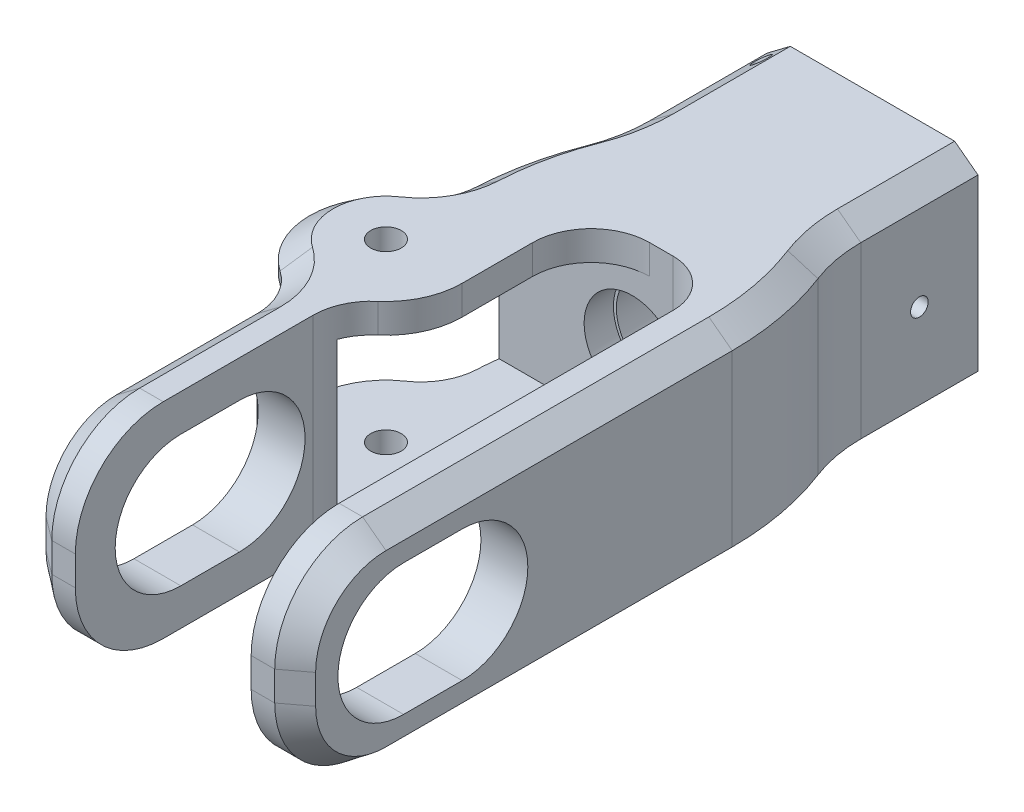
SolidWorks part; units mm, degrees
ref_plane "Front Plane" through (0, 0, 0) normal (0, 0, 1) x (1, 0, 0)
ref_plane "Top Plane" through (0, 0, 0) normal (0, 1, 0) x (1, 0, 0)
ref_plane "Right Plane" through (0, 0, 0) normal (1, 0, 0) x (0, 0, -1)
sketch "Sketch1" plane through (0, 0, 0) normal (0, 0, 1) x (1, 0, 0)
  line L1 (23, 17.5) -> (-23, 17.5)
  line L2 (23, 17.5) -> (23, -17.5)
  line L3 (23, -17.5) -> (-23, -17.5)
  line L4 (-23, 17.5) -> (-23, -17.5)
  line L5 (23, 17.5) -> (-23, -17.5) construction
  line L6 (23, -17.5) -> (-23, 17.5) construction
  circle A0 centre (0, 0) radius 7.7
  dimension "D1" = 15.4
  dimension "D2" = 46
  dimension "D3" = 35
extrude "Boss-Extrude1" add sketch "Sketch1" along normal blind 36
sketch "Sketch2" plane through (0, 0, 0) normal (0, 0, -1) x (-1, 0, 0)
  circle A0 centre (0, 0) radius 7.7
  circle A1 centre (0, 0) radius 11
  circle A2 centre (0, 0) radius 7.7 construction
  dimension "D1" = 22
extrude "Boss-Extrude2" add sketch "Sketch2" along normal blind 1
sketch "Sketch5" plane through (0, 0, 36) normal (0, 0, 1) x (1, 0, 0)
  line L0 (-23, -17.5) -> (23, -17.5) construction
  line L1 (-23, 17.5) -> (-15, 17.5)
  line L2 (-23, 17.5) -> (-23, -17.5)
  line L3 (-23, -17.5) -> (-15, -17.5)
  line L4 (-15, 17.5) -> (-15, -17.5)
  dimension "D1" = 8
extrude "Boss-Extrude4" add sketch "Sketch5" along normal blind 85
sketch "Sketch3" plane through (0, 0, 36) normal (0, 0, 1) x (1, 0, 0)
  line L1 (-15, 17.5) -> (23, 17.5)
  line L2 (-15, 17.5) -> (-15, -17.5)
  line L3 (-15, -17.5) -> (23, -17.5)
  line L4 (23, 17.5) -> (23, -17.5)
  circle A0 centre (0, 0) radius 8.2
  dimension "D1" = 16.4
extrude "Boss-Extrude3" add sketch "Sketch3" along normal blind 5
sketch "Sketch4" plane through (0, 0, 0) normal (0, 1, 0) x (1, 0, 0)
  line L0 (23, -41) -> (-15, -41) construction
  circle A0 centre (-20, -63) radius 2.6
  dimension "D2" = 5.2
  dimension "D1" = 22
  dimension "D3" = 20
extrude "Cut-Extrude1" cut sketch "Sketch4" against normal through all both and the other way through all
sketch "Sketch10" plane through (0, 17.5, 0) normal (0, 1, 0) x (1, 0, 0)
  line L0 (-23, -121) -> (-23, 0) construction
  line L1 (-23, -50.3509) -> (-23, -75.6491)
  line L2 (-15, -121) -> (-15, -41) construction
  line L3 (-15, -41) -> (-15, -75)
  line L4 (-7, -63) -> (-7, -41)
  line L5 (23, -41) -> (-15, -41) construction
  line L6 (-7, -41) -> (-15, -41)
  arc A0 (-23, -50.3509) -> (-23, -75.6491) centre (-20, -63) ccw
  arc A2 (-15, -75) -> (-7, -63) centre (-20, -63) ccw
  dimension "D1" = 13
  dimension "D2" = 13
extrude "Boss-Extrude6" add sketch "Sketch10" against normal up to surface (35 mm away) up to face at (-20, -17.5, 65.6)
sketch "Sketch6" plane through (0, 0, 0) normal (0, 1, 0) x (1, 0, 0)
  line L5 (-33, -41) -> (-33, -77)
  line L6 (-33, -77) -> (-7, -77)
  line L7 (-7, -77) -> (-7, -41)
  line L8 (-7, -41) -> (-33, -41)
  circle A0 centre (-20, -63) radius 2.6 construction
  point P0 (-20, -59)
  point P3 (-33, -59)
  point P8 (-20, -41)
  point P12 (-20, -77)
  dimension "D1" = 14
  dimension "D2" = 26
sketch "Sketch9" plane through (0, 0, 41) normal (0, 0, 1) x (1, 0, 0)
  line L0 (-7, -17.5) -> (23, -17.5) construction
  line L1 (23, 17.5) -> (15, 17.5)
  line L2 (23, 17.5) -> (23, -17.5)
  line L3 (23, -17.5) -> (15, -17.5)
  line L4 (15, 17.5) -> (15, -17.5)
  line L5 (23, 17.5) -> (-7, 17.5) construction
  dimension "D1" = 8
extrude "Boss-Extrude5" add sketch "Sketch9" along normal blind 80
fillet "Fillet1" radius 15 4 edges at (-19, -17.5, 121) (-19, 17.5, 121) (19, -17.5, 121) (19, 17.5, 121)
fillet "Fillet9" radius 10 3 edges at (-23, 0, 50.3509) (-23, 0, 75.6491) (-15, 0, 75)
fillet "Fillet11" radius 8 1 edges at (15, 0, 41)
sketch "Sketch20" plane through (0, 17.5, 0) normal (0, 1, 0) x (1, 0, 0)
  line L0 (-18, 0) -> (-18, -20)
  line L1 (-23, -44.0263) -> (-23, 0) construction
  line L2 (23, 0) -> (-23, 0) construction
  line L3 (-18, 0) -> (-23, 0)
  line L4 (-23, 0) -> (-23, -35)
  line L5 (18, -20) -> (18, 0)
  line L6 (18, 0) -> (23, 0)
  line L7 (23, 0) -> (23, -35)
  line L8 (23, -106) -> (23, 0) construction
  arc A0 (-18, -20) -> (-23, -35) centre (-43, -20) cw
  arc A1 (23, -35) -> (18, -20) centre (43, -20) cw
  dimension "D2" = 25
  dimension "D1" = 5
  dimension "D3" = 35
  dimension "D4" = 5
extrude "Cut-Extrude2" cut sketch "Sketch20" against normal up to surface (35 mm away) up to face at (-20, -17.5, 65.6)
fillet "Fillet12" radius 50 2 edges at (23, 0, 35) (-23, 0, 35)
extrude "Cut-Extrude3" cut sketch "Sketch6" against normal mid plane 25
fillet "Fillet13" radius 10 2 edges at (-7, -15, 41) (-7, 15, 41)
ref_axis "Axis1" through (-20, 12.5, 63) along (0, 1, 0)
sketch "Sketch21" plane through (-23, 0, 0) normal (-1, 0, 0) x (0, 0, 1)
  line L1 (63, 12.5) -> (63, 17.5) construction
  line L2 (55, 0) -> (-55, 0) construction
  circle A0 centre (98, 0) radius 2.5 construction
  dimension "D2" = 5
  dimension "D1" = 35
sketch "Sketch22" plane through (-23, 0, 0) normal (-1, 0, 0) x (0, 0, 1)
  line L0 (93, 0) -> (103, 0) construction
  line L1 (93, 11.2) -> (103, 11.2)
  line L2 (93, -11.2) -> (103, -11.2)
  arc A0 (93, 11.2) -> (93, -11.2) centre (93, 0) ccw
  arc A1 (103, -11.2) -> (103, 11.2) centre (103, 0) ccw
  point P2 (98, 0)
  dimension "D1" = 22.4
  dimension "D2" = 10
extrude "Cut-Extrude4" cut sketch "Sketch22" against normal up to surface (46 mm away) up to face at (23, 0, 92.3441)
chamfer "Chamfer1" distance 3 angle 53 28 edges at (18, -17.5, 10) (18.4202, -17.5, 24.5644) (22.1596, -17.5, 37.7971) (23, -17.5, 76.4629) (23, -13.1066, 116.6066) (18, 17.5, 10) (23, 0, 121) (18.4202, 17.5, 24.5644) (23, 13.1066, 116.6066) (22.1596, 17.5, 37.7971) (23, 17.5, 76.4629) (-18, -17.5, 10) (-18.427, -17.5, 24.601) (-21.9716, -17.5, 36.6622) (-24.2773, -17.5, 48.9165) (-33, -17.5, 63) (-24.1535, -17.5, 77.3111) (-23, -17.5, 93.9868) (-23, -13.1066, 116.6066) (-23, 0, 121) (-23, 13.1066, 116.6066) (-24.1535, 17.5, 77.3111) (-33, 17.5, 63) (-18, 17.5, 10) (-24.2773, 17.5, 48.9165) (-18.427, 17.5, 24.601) (-23, 17.5, 93.9868) (-21.9716, 17.5, 36.6622) first distance on face at (18, 0, 10) first distance on face at (18.6268, 0, 24.526) first distance on face at (21.7465, 0, 37.8738) first distance on face at (23, 0, 98) first distance on face at (-18, 0, 10) first distance on face at (-18.6369, 0, 24.5617) first distance on face at (-22.2682, 0, 39.7496) first distance on face at (-24.7289, -15, 48.6633) first distance on face at (-30.1739, -15, 63) first distance on face at (-24.763, 0, 77.5375) first distance on face at (-23, 0, 98.9959) first distance on face at (-30.1739, 15, 63) first distance on face at (-24.7289, 15, 48.6633)
sketch "Sketch23" plane through (18, 0, 0) normal (1, 0, 0) x (0, 0, -1)
  line L0 (0, -14.5) -> (0, 14.5) construction
  line L1 (55, 0) -> (-55, 0) construction
  circle A0 centre (-10, 0) radius 1.5
  dimension "D1" = 3
  dimension "D2" = 10
extrude "Cut-Extrude5" cut sketch "Sketch23" against normal up to surface (10.3 mm away) up to face at (7.7, 0, 36)
sketch "Sketch25" plane through (-13.4884, 17.8997, 0) normal (-0.6018, 0.7986, 0) x (0.7986, 0.6018, 0)
  line L0 (-5.6491, 0) -> (-0.6642, 0) construction
  circle A0 centre (-3.1567, -3) radius 1.5
  point P5 (-3.1567, 0)
  dimension "D1" = 3
  dimension "D2" = 3
extrude "Cut-Extrude6" cut sketch "Sketch25" against normal blind 10
